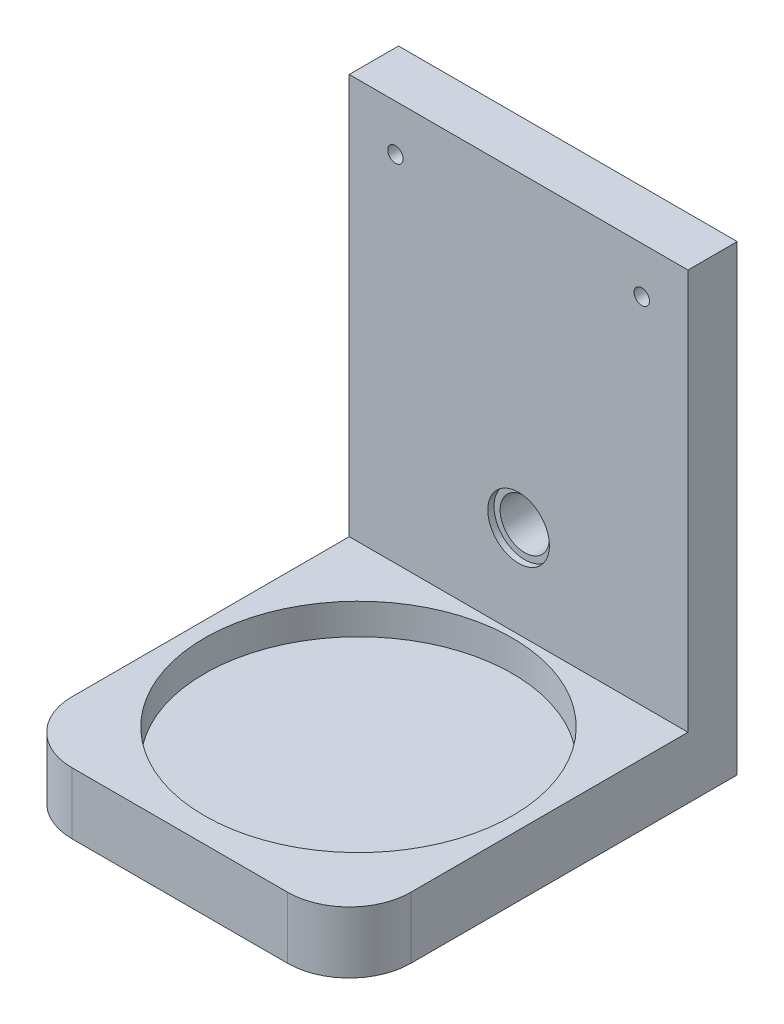
SolidWorks part; units mm, degrees
ref_plane "Front Plane" through (0, 0, 0) normal (0, 0, 1) x (1, 0, 0)
ref_plane "Top Plane" through (0, 0, 0) normal (0, 1, 0) x (1, 0, 0)
ref_plane "Right Plane" through (0, 0, 0) normal (1, 0, 0) x (0, 0, -1)
sketch "Sketch1" plane through (0, 0, 0) normal (0, 0, 1) x (1, 0, 0)
  line L0 (0, 150) -> (0, 0) construction
  line L1 (55, 0) -> (-55, 0)
  line L2 (55, 0) -> (55, 150)
  line L3 (55, 150) -> (-55, 150)
  line L4 (-55, 0) -> (-55, 150)
  circle A1 centre (40, 135) radius 2.5
  circle A2 centre (-40, 135) radius 2.5
  point P7 (0, 0)
  dimension "D4" = 15
  dimension "D5" = 15
  dimension "D1" = 150
  dimension "D2" = 110
extrude "Boss-Extrude1" add sketch "Sketch1" along normal blind 16
sketch "Sketch4" plane through (0, 0, 0) normal (0, 1, 0) x (1, 0, 0)
  line L0 (55, -16) -> (-55, -16) construction
  line L1 (-55, -16) -> (55, -16)
  line L2 (-55, -16) -> (-55, -126)
  line L3 (-55, -126) -> (55, -126)
  line L4 (55, -16) -> (55, -126)
  line L6 (0, -16) -> (0, -126) construction
  line L7 (-55, -71) -> (55, -71) construction
  point P10 (0, 0)
  point P11 (0, 0)
  dimension "D1" = 110
  dimension "D2" = 110
sketch "Sketch5" plane through (0, 0, 16) normal (0, 0, 1) x (1, 0, 0)
  line L0 (0, 0) -> (0, 150) construction
  line L1 (55, 150) -> (-55, 150) construction
  line L2 (-55, 75) -> (55, 75) construction
  line L3 (-55, 150) -> (-55, 0) construction
  line L4 (55, 0) -> (55, 150) construction
  circle A0 centre (0, 50) radius 10
  dimension "D1" = 20
  dimension "D2" = 50
extrude "Boss-Extrude2" add sketch "Sketch4" along normal blind 20 contours L2 L3 L4 L1
sketch "Sketch6" plane through (0, 20, 0) normal (0, 1, 0) x (1, 0, 0)
  line L0 (-10, -16) -> (10, -16) construction
  circle A0 centre (0, -68) radius 50
  point P0 (0, -18)
  point P1 (0, -16)
  dimension "D1" = 100
  dimension "D2" = 2
extrude "Cut-Extrude1" cut sketch "Sketch6" against normal blind 10 contours A0
fillet "Fillet1" radius 20 2 edges at (55, 10, 126) (-55, 10, 126)
sketch "Sketch7" plane through (0, 0, 16) normal (0, 0, 1) x (1, 0, 0)
  circle A0 centre (0, 50) radius 8
  dimension "D1" = 16
extrude "Cut-Extrude4" cut sketch "Sketch7" against normal through all
extrude "Cut-Extrude5" cut sketch "Sketch5" against normal blind 2
